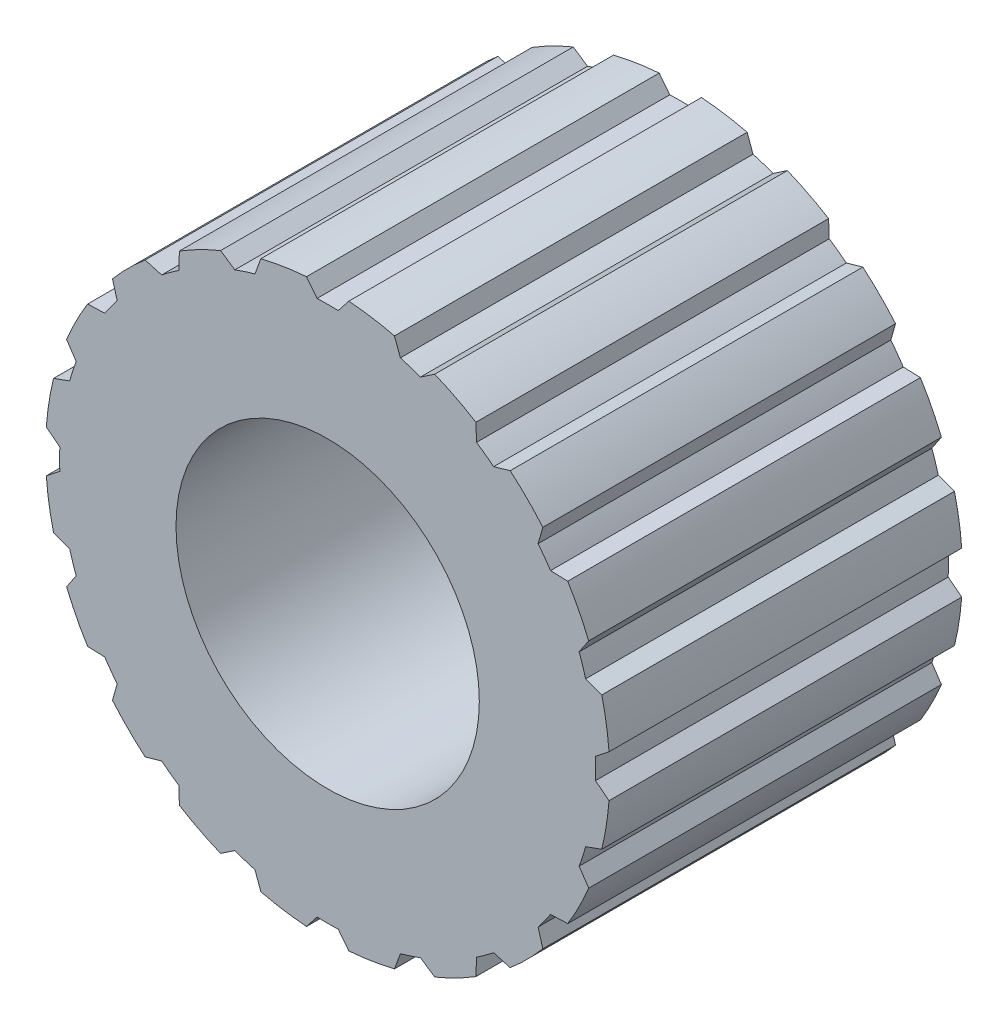
SolidWorks part; units mm, degrees
material "Brass"
ref_plane "Front Plane" through (0, 0, 0) normal (0, 0, 1) x (1, 0, 0)
ref_plane "Top Plane" through (0, 0, 0) normal (0, 1, 0) x (1, 0, 0)
ref_plane "Right Plane" through (0, 0, 0) normal (1, 0, 0) x (0, 0, -1)
ref_axis "CentralAxis" through (0, 0, 51.25) along (0, 0, -1)
sketch "BodyS" plane through (0, 0, 0) normal (0, 0, -1) x (-1, 0, 0)
  circle A0 centre (0, 0) radius 4
  dimension "C" = 8
extrude "Body" add sketch "BodyS" along normal mid plane 5
sketch "EngagementCutS" plane through (0, 0, 0) normal (0, 0, -1) x (-1, 0, 0)
  line L0 (0, 3.8) -> (0, 4) construction
  line L1 (0.3, 3.9887) -> (0.15, 3.797)
  line L2 (-0.3, 3.9887) -> (-0.15, 3.797)
  circle A0 centre (0, 0) radius 4 construction
  arc A1 (0.3, 3.9887) -> (-0.3, 3.9887) centre (0, 0) ccw
  circle A2 centre (0, 0) radius 3.8
  arc A3 (0.15, 3.797) -> (-0.15, 3.797) centre (0, 0) ccw
  dimension "MinorDiameterWidthCut" = 0.3
  dimension "MajorDiameterWidthCut" = 0.6
  dimension "Depth" = 0.2
extrude "EngagementCut" cut sketch "EngagementCutS" against normal through all both and the other way through all
sketch "MajorDiameterCutS" plane through (0, 0, 2.5) normal (0, 0, 1) x (1, 0, 0)
  circle A0 centre (0, 0) radius 2.15
  dimension "Thread Od" = 4.3
pattern_circular "ECCP" count 20 over 360 about axis through (0, 0, 51.25) along (0, 0, -1) of "EngagementCut"
extrude "MajorDiameterCut" cut sketch "MajorDiameterCutS" against normal through all
